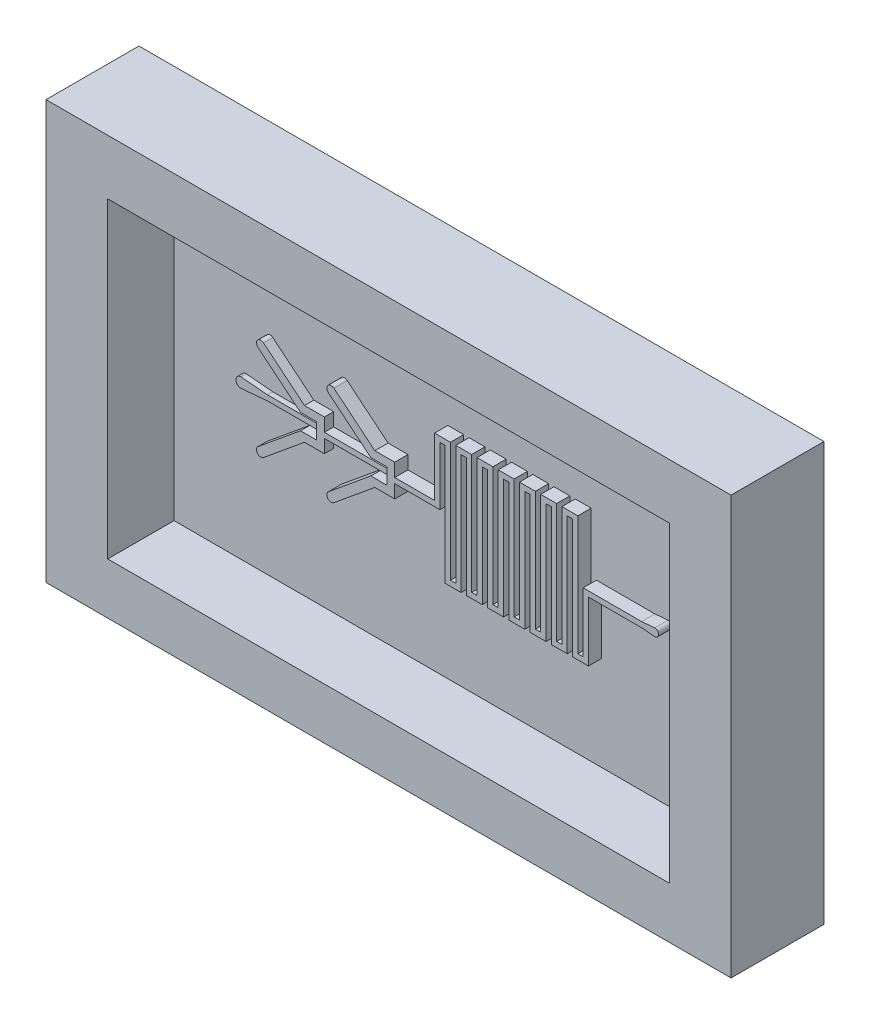
SolidWorks part; units mm, degrees
note: The reader was unsure of these and kept them because the rebuilt part matched: shared geometry of "Sketch1<7>", "Sketch1<8>".
ref_plane "Front Plane" through (0, 0, 0) normal (0, 0, 1) x (1, 0, 0)
ref_plane "Top Plane" through (0, 0, 0) normal (0, 1, 0) x (1, 0, 0)
ref_plane "Right Plane" through (0, 0, 0) normal (1, 0, 0) x (0, 0, -1)
sketch "Sketch1" plane through (0, 0, 0) normal (0, 0, 1) x (1, 0, 0)
  line L0 (-4.8, 0.0927) -> (-5.7962, 0.1799)
  line L5 (0, 0.2927) -> (-0.6, 0.2927)
  line L6 (0, 0.0927) -> (0, 0.2927)
  line L7 (0, -0.1073) -> (0, -0.3073)
  line L8 (-2.5, 0.0927) -> (0, 0.0927)
  line L10 (-0.45, 0.5927) -> (-1.9914, 1.8612)
  line L11 (-0.6, 0.2927) -> (-2.1992, 1.6087)
  line L12 (-2.5, -0.1073) -> (0, -0.1073)
  line L16 (0, 0.2927) -> (0, 0.0927)
  line L17 (-2.8, 0.0927) -> (-2.8, -0.1073)
  line L18 (0.3, 0.5927) -> (0.3, 0.0927)
  line L19 (0.3, 0.5927) -> (-0.45, 0.5927)
  line L20 (0.3, -0.6073) -> (0.3, -0.1073)
  line L21 (0, 0.0927) -> (0, -0.1073)
  line L22 (0, -0.3073) -> (-0.6, -0.3073)
  line L23 (0.3, -0.6073) -> (-0.45, -0.6073)
  line L24 (-0.45, -0.6073) -> (-1.9914, -1.8758)
  line L25 (-0.6, -0.3073) -> (-2.1992, -1.6233)
  line L26 (0.8, 0.0927) -> (1.8, 0.0927)
  line L27 (0.8, -0.1073) -> (2, -0.1073)
  line L28 (0.8, 0.0927) -> (0.3, 0.0927)
  line L29 (0.8, -0.1073) -> (0.3, -0.1073)
  line L30 (1.8, 0.0927) -> (1.8, 2.2927)
  line L31 (2, -0.1073) -> (2, 2.0906)
  line L32 (2, 2.0906) -> (2.2, 2.0906)
  line L33 (1.8, 2.2927) -> (2.4, 2.2927)
  line L34 (2.2, 2.0906) -> (2.2, -2.4094)
  line L35 (2.4, 2.2927) -> (2.4, -2.2073)
  line L36 (2.4, -2.2073) -> (2.6, -2.2073)
  line L37 (2.2, -2.4094) -> (2.8, -2.4094)
  line L38 (2.6, -2.2073) -> (2.6, 2.2927)
  line L39 (2.8, -2.4094) -> (2.8, 2.0906)
  line L40 (2.6, 2.2927) -> (3.2, 2.2927)
  line L41 (2.8, 2.0906) -> (3, 2.0906)
  line L42 (3, 2.0906) -> (3, -2.4094)
  line L43 (3.2, 2.2927) -> (3.2, -2.2073)
  line L44 (3.2, -2.2073) -> (3.4, -2.2073)
  line L45 (3, -2.4094) -> (3.6, -2.4094)
  line L46 (3.4, -2.2073) -> (3.4, 2.2927)
  line L47 (3.6, -2.4094) -> (3.6, 2.0906)
  line L48 (3.4, 2.2927) -> (4, 2.2927)
  line L49 (3.6, 2.0906) -> (3.8, 2.0906)
  line L50 (3.8, 2.0906) -> (3.8, -2.4094)
  line L51 (4, 2.2927) -> (4, -2.2073)
  line L52 (4, -2.2073) -> (4.2, -2.2073)
  line L53 (3.8, -2.4094) -> (4.4, -2.4094)
  line L54 (4.2, -2.2073) -> (4.2, 2.2927)
  line L55 (4.4, -2.4094) -> (4.4, 2.0906)
  line L56 (4.2, 2.2927) -> (4.8, 2.2927)
  line L57 (4.4, 2.0906) -> (4.6, 2.0906)
  line L58 (4.6, 2.0906) -> (4.6, -2.4094)
  line L59 (4.8, 2.2927) -> (4.8, -2.2073)
  line L60 (4.8, -2.2073) -> (5, -2.2073)
  line L61 (4.6, -2.4094) -> (5.2, -2.4094)
  line L62 (5, -2.2073) -> (5, 2.2927)
  line L63 (5.2, -2.4094) -> (5.2, 2.0906)
  line L64 (5, 2.2927) -> (5.6, 2.2927)
  line L65 (5.2, 2.0906) -> (5.4, 2.0906)
  line L66 (5.4, 2.0906) -> (5.4, -2.4094)
  line L67 (5.6, 2.2927) -> (5.6, -2.2073)
  line L68 (5.6, -2.2073) -> (5.8, -2.2073)
  line L69 (5.4, -2.4094) -> (6, -2.4094)
  line L70 (5.8, -2.2073) -> (5.8, 2.2927)
  line L71 (6, -2.4094) -> (6, 2.0906)
  line L72 (5.8, 2.2927) -> (6.4, 2.2927)
  line L73 (6, 2.0906) -> (6.2, 2.0906)
  line L74 (6.2, 2.0906) -> (6.2, -2.4094)
  line L75 (6.4, 2.2927) -> (6.4, -2.2073)
  line L76 (6.4, -2.2073) -> (6.6, -2.2073)
  line L77 (6.2, -2.4094) -> (6.8, -2.4094)
  line L78 (6.6, -2.2073) -> (6.6, 2.2927)
  line L79 (6.8, -2.4094) -> (6.8, 2.0906)
  line L80 (6.6, 2.2927) -> (7.2, 2.2927)
  line L81 (6.8, 2.0906) -> (7, 2.0906)
  line L82 (7, 2.0906) -> (7, -2.4094)
  line L83 (7.2, 2.2927) -> (7.2, -2.2073)
  line L84 (7.2, -2.2073) -> (7.4, -2.2073)
  line L85 (7, -2.4094) -> (7.6, -2.4094)
  line L86 (9.6, 0.0427) -> (10.0981, 0.0863)
  line L87 (9.6, -0.1594) -> (10.0981, -0.203)
  line L88 (7.4, 0.0427) -> (9.6, 0.0427)
  line L89 (7.6, -0.1594) -> (9.6, -0.1594)
  line L90 (7.4, -2.2073) -> (7.4, 0.0427)
  line L91 (7.6, -2.4094) -> (7.6, -0.1594)
  line L92 (-2.5, 0.5927) -> (-2.5, 0.0927)
  line L93 (7.6, -2.4094) -> (7.6, 2.0906) [skipped]
  line L94 (7.4, -2.2073) -> (7.4, 2.2927) [skipped]
  line L95 (-2.5, -0.1073) -> (-2.5, -0.6073)
  line L100 (-2.8, 0.0927) -> (-2.8, 0.2927)
  line L101 (-2.8, -0.1073) -> (-2.8, -0.3073)
  line L102 (-2.5, -0.6073) -> (-3.25, -0.6073)
  line L103 (-2.8, -0.3073) -> (-3.4, -0.3073)
  line L104 (-2.8, 0.2927) -> (-3.4, 0.2927)
  line L105 (-2.5, 0.5927) -> (-3.25, 0.5927)
  line L106 (-3.25, 0.5927) -> (-4.7914, 1.8612)
  line L107 (-3.4, 0.2927) -> (-4.9992, 1.6087)
  line L108 (-3.4, -0.3073) -> (-4.9992, -1.6233)
  line L109 (-3.25, -0.6073) -> (-4.7914, -1.8758)
  line L110 (-2.8, 0.0927) -> (-4.8, 0.0927)
  line L111 (-2.8, -0.1073) -> (-4.8, -0.1073)
  line L112 (-4.8, -0.1073) -> (-5.7962, -0.1944)
  line L117 (-2.5, 0.5927) -> (-2.5, 0.0927)
  line L118 (-2.5, -0.1073) -> (-2.5, -0.6073)
  arc A0 (-1.9914, 1.8612) -> (-2.1992, 1.6087) centre (-2.0953, 1.735) ccw
  arc A1 (-1.9914, -1.8758) -> (-2.1992, -1.6233) centre (-2.0953, -1.7495) cw
  arc A2 (10.0981, 0.0863) -> (10.0981, -0.203) centre (10.0981, -0.0583) cw
  arc A3 (-4.7914, 1.8612) -> (-4.9992, 1.6087) centre (-4.8953, 1.735) ccw
  arc A4 (-4.7914, -1.8758) -> (-4.9992, -1.6233) centre (-4.8953, -1.7495) cw
  arc A5 (-5.7962, 0.1799) -> (-5.7962, -0.1944) centre (-5.7962, -0.0073) ccw
  point P0 (0, 0)
  point P14 (0, -0.0073)
  dimension "D7" = 1
  dimension "D4" = 0.2
  dimension "D1" = 0.2
  dimension "D2" = 0.2
  dimension "D3" = 0.2
  dimension "D5" = 0.6
  dimension "D8" = 1.2
  dimension "D9" = 2.2
  dimension "D10" = 0.2
  dimension "D11" = 0.6
  dimension "D12" = 4.5
  dimension "D13" = 4.5
  dimension "D14" = 0.2
  dimension "D15" = 0.6
  dimension "D16" = 4.5
  dimension "D17" = 7
  dimension "D18" = 2.2
  dimension "D19" = 2
  dimension "D20" = 0.5
  dimension "D21" = 175
  dimension "D22" = 0.5
  dimension "D23" = 175
  dimension "D27" = 1
  dimension "D28" = 175
  dimension "D29" = 1
  dimension "D30" = 175
  dimension "D26" = 2
extrude "Boss-Extrude4" add sketch "Sketch1" along normal blind 0.2 contours L0 A5 L112 L111 L17 L110
extrude "Boss-Extrude5" add sketch "Sketch1<7>" along normal blind 0.35
sketch "Sketch1<7>" plane through (0, 0, 0) normal (0, 0, 1) x (1, 0, 0) same geometry as "Sketch1"
extrude "Boss-Extrude6" add sketch "Sketch1<8>" along normal blind 0.5
sketch "Sketch1<8>" plane through (0, 0, 0) normal (0, 0, 1) x (1, 0, 0) same geometry as "Sketch1"
sketch "Sketch5" plane through (0, 0, 0) normal (0, 0, -1) x (-1, 0, 0)
  line L1 (8.514, -5.9722) -> (-12.6443, -5.9722)
  line L2 (8.514, -5.9722) -> (8.514, 5.7793)
  line L3 (8.514, 5.7793) -> (-12.6443, 5.7793)
  line L4 (-12.6443, -5.9722) -> (-12.6443, 5.7793)
extrude "Boss-Extrude7" add sketch "Sketch5" along normal blind 1
sketch "Sketch8" plane through (0, 0, -1) normal (0, 0, -1) x (-1, 0, 0)
  line L1 (-14.9727, 7.8542) -> (10.8372, 7.8542)
  line L2 (-14.9727, 7.8542) -> (-14.9727, -7.9029)
  line L3 (-14.9727, -7.9029) -> (10.8372, -7.9029)
  line L4 (10.8372, 7.8542) -> (10.8372, -7.9029)
  line L5 (-12.6443, 5.7793) -> (8.514, 5.7793)
  line L6 (-12.6443, 5.7793) -> (-12.6443, -5.9722)
  line L7 (-12.6443, -5.9722) -> (8.514, -5.9722)
  line L8 (8.514, 5.7793) -> (8.514, -5.9722)
extrude "Boss-Extrude8" add sketch "Sketch8" against normal blind 3.5
